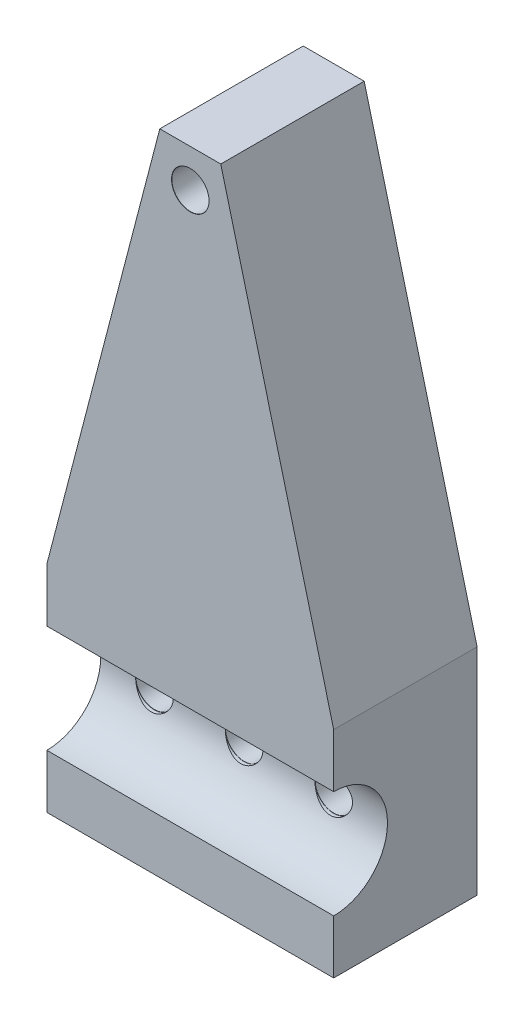
SolidWorks part; units mm, degrees
ref_plane "Front Plane" through (0, 0, 0) normal (0, 0, 1) x (1, 0, 0)
ref_plane "Top Plane" through (0, 0, 0) normal (0, 1, 0) x (1, 0, 0)
ref_plane "Right Plane" through (0, 0, 0) normal (1, 0, 0) x (0, 0, -1)
sketch "Sketch1" plane through (0, 0, 0) normal (0, 0, 1) x (1, 0, 0)
  line L0 (-25.4, 19.05) -> (-5.3997, 95.8011)
  line L1 (25.4, -19.05) -> (-25.4, -19.05)
  line L2 (25.4, -19.05) -> (25.4, 19.05)
  line L3 (25.4, 19.05) -> (-25.4, 19.05)
  line L4 (-25.4, -19.05) -> (-25.4, 19.05)
  line L5 (25.4, -19.05) -> (-25.4, 19.05) construction
  line L6 (25.4, 19.05) -> (-25.4, -19.05) construction
  line L7 (-5.3997, 95.8011) -> (5.3997, 95.8011)
  line L8 (5.3997, 95.8011) -> (25.4, 19.05)
  line L9 (-15.875, 0) -> (15.875, 0) construction
  line L10 (0, 95.8011) -> (0, 89.0924) construction
  point P0 (0, 0)
  point P8 (0, 95.8011)
  point P9 (0, 0)
  point P14 (0, 94.3285)
  point P15 (0, 101.2008)
  point P16 (0, 89.0924)
  point P17 (0, 94.8194)
  point P18 (-5.3997, 95.8011)
  dimension "D1" = 50.8
  dimension "D2" = 38.1
  dimension "D4" = 31.75
extrude "Boss-Extrude1" add sketch "Sketch1" along normal blind 25.4 contours L8 L7 L0 L3 | L4 L1 L2 L3 region at (0, 49.1189, 0) region at (0, 0, 0)
sketch "Sketch2" plane through (0, 0, 25.4) normal (0, 0, 1) x (1, 0, 0)
  line L0 (-25.4, 0) -> (25.4, 0)
  line L1 (-25.4, -19.05) -> (-25.4, 19.05) construction
  line L2 (25.4, -19.05) -> (25.4, 19.05) construction
sweep "Cut-Sweep1" cut path "Sketch2" circular profile diameter 19.05 parameters "D3"=19.05
hole_wizard "M6 Clearance Hole1" positions "3DSketch1" profile "Sketch9" hole size "M6" standard "ANSI Metric" end condition through all
sketch3d "3DSketch1"
  point P0 (0, 0, 15.875)
  point P4 (-15.875, 0, 15.875)
  point P6 (15.875, 0, 15.875)
  point P8 (0, 89.0924, 25.4)
sketch "Sketch9" plane through (0, 0, 15.875) normal (1, 0, 0) x (0, -1, 0)
  line L0 (0, 0) -> (0, 15.875)
  line L1 (0, 15.875) -> (3.3, 15.875)
  line L2 (3.3, 15.875) -> (3.3, 0.025)
  line L3 (3.3, 0.025) -> (3.325, 0)
  line L5 (3.325, 0) -> (0, 0)
  line L6 (-3.3, 0.025) -> (-3.325, 0) construction
  line L11 (0, -6.35) -> (0, 107.95) construction
  dimension "Thru Hole Dia." = 6.6
  dimension "Thru Hole Depth" = 15.875
  dimension "Near C'Sink Dia." = 6.65
  dimension "Near C'Sink Angle" = 90
equation "\"Rover_Length\"= 25in"
equation "\"Rover_Width\"= 18in"
equation "\"Rover_Height\"= 12in"
equation "\"Chassis_Wheelbase\"= 28in"
equation "\"Chassis_WheelDiam\"= 171mm"
equation "\"Chassis_ArmDiamWidth\"= 0.75in"
equation "\"Chassis_ArmAngle\"= 135deg"
equation "\"Chassis_ArmHeight\"= 8in"
equation "\"Chassis_HubMountOD\"= 3in"
equation "\"Chassis_WheelBoltHole\"= 36mm"
equation "\"Chassis_WheelBoltNum\"= 4"
equation "\"Chassis_DiffBarLength\"= 12in"
equation "\"Chassis_DiffBarWidth\"= 1in"
equation "\"Chassis_DiffBarHeight\"= 0.5in"
equation "\"Chassis_DiffLinkage_Length\"= 2.5in"
equation "\"Chassis_MountBracketThickness\"= 0.125in"
equation "\"Chassis_MountBracketWidth\"= 3in"
equation "\"Chassis_MountBacketOverlap\"= 0.5in"
equation "\"Chassis_ArmShaftDiam\"= 0.75in"
equation "\"Chassis_ArmHoleSpacing\" = 1.25in"
equation "\"D4@Sketch1\"=\"Chassis_ArmHoleSpacing\""
